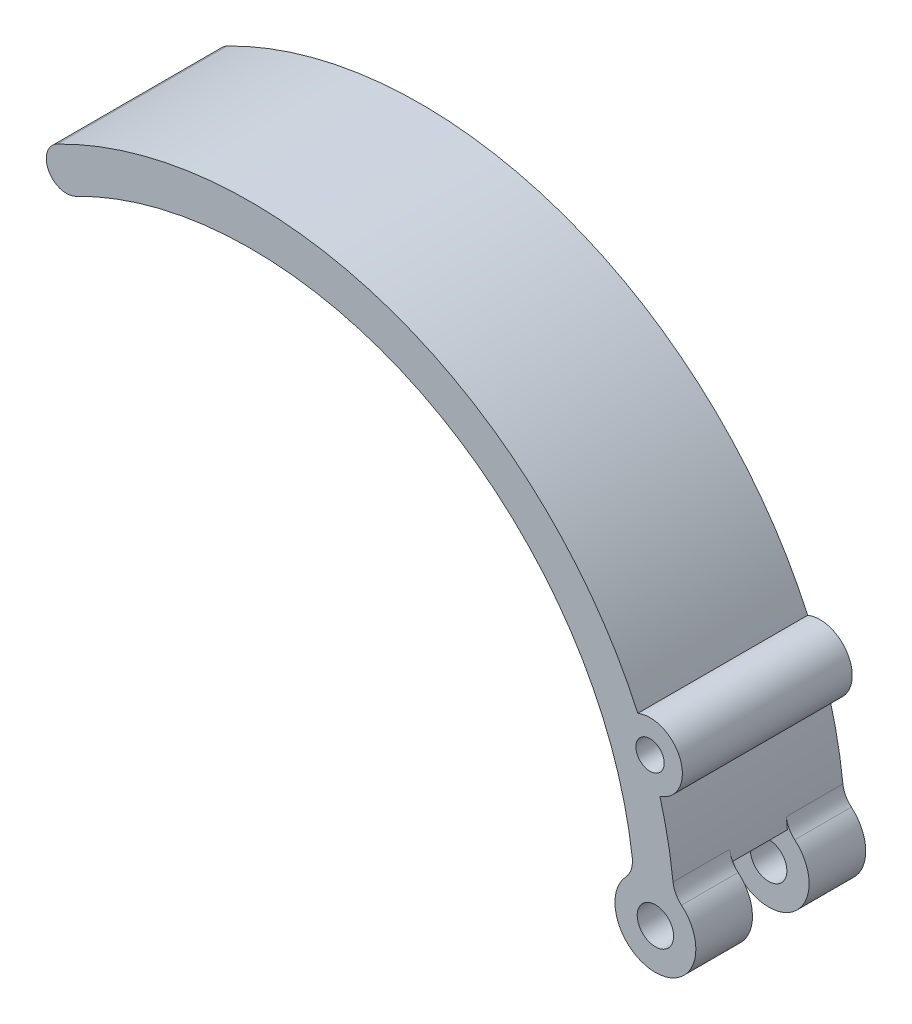
SolidWorks part; units mm, degrees
ref_plane "Plan de face" through (0, 0, 0) normal (0, 0, 1) x (1, 0, 0)
ref_plane "Plan de dessus" through (0, 0, 0) normal (0, 1, 0) x (1, 0, 0)
ref_plane "Plan de droite" through (0, 0, 0) normal (1, 0, 0) x (0, 0, -1)
sketch "Esquisse1" plane through (0, 0, 0) normal (0, 0, 1) x (1, 0, 0)
  line L0 (0, 0) -> (-25, 43.3013) construction
  line L1 (0, 0) -> (50, 0) construction
  arc A0 (50, 0) -> (-25, 43.3013) centre (0, 0) ccw
  dimension "D1" = 50
  dimension "D2" = 120
extrude "Extru.-Mince1" add sketch "Esquisse1" along normal blind 21 thin thin type mid plane wall 5
sketch "Esquisse4" plane through (0, 0, 21) normal (0, 0, 1) x (1, 0, 0)
  line L0 (52.5, 0) -> (47.5, 0) construction
  circle A0 centre (50, 0) radius 5
  dimension "D1" = 10
extrude "Boss.-Extru.2" add sketch "Esquisse4" against normal up to vertex (21 mm away) up to point (-26.25, 45.4663, 0)
sketch "Esquisse5" plane through (0, 0, 21) normal (0, 0, 1) x (1, 0, 0)
  circle A0 centre (50, 0) radius 2.25
  dimension "D1" = 4.5
extrude "Enlèv. mat.-Extru.2" cut sketch "Esquisse5" against normal through all both and the other way through all
sketch "Esquisse6" plane through (0, 0, 21) normal (0, 0, 1) x (1, 0, 0)
  circle A0 centre (50, 0) radius 5
  arc A1 (47.3125, 4.2163) -> (52.3125, 4.4331) centre (50, 0) ccw construction
extrude "Enlèv. mat.-Extru.3" cut sketch "Esquisse6" against normal blind 7 from offset 7 offset against normal yes
fillet "Congé4" radius 3 4 edges at (52.3125, 4.4331, 3.5) (52.3125, 4.4331, 17.5) (47.3125, 4.2163, 17.5) (47.3125, 4.2163, 3.5)
fillet "Congé6" radius 2.5 2 edges at (-26.25, 45.4663, 10.5) (-23.75, 41.1362, 10.5)
sketch "Esquisse7" plane through (0, 0, 21) normal (0, 0, 1) x (1, 0, 0)
  line L0 (49.3339, 17.9561) -> (0, 0) construction
  line L1 (0, 0) -> (50, 0) construction
  arc A0 (47.8236, 21.66) -> (50.5578, 14.1479) centre (49.3339, 17.9561) cw
  arc A1 (52.1807, 5.781) -> (-23.9439, 46.722) centre (0, 0) ccw construction
  arc A2 (50.5578, 14.1479) -> (47.8236, 21.66) centre (0, 0) ccw
  dimension "D1" = 4
  dimension "D2" = 20
extrude "Boss.-Extru.3" add sketch "Esquisse7" against normal up to vertex (21 mm away) up to point (52.1807, 5.781, 0)
sketch "Esquisse8" plane through (0, 0, 21) normal (0, 0, 1) x (1, 0, 0)
  circle A0 centre (49.3339, 17.9561) radius 1.75
  dimension "D1" = 3.5
extrude "Enlèv. mat.-Extru.4" cut sketch "Esquisse8" against normal through all both and the other way through all
